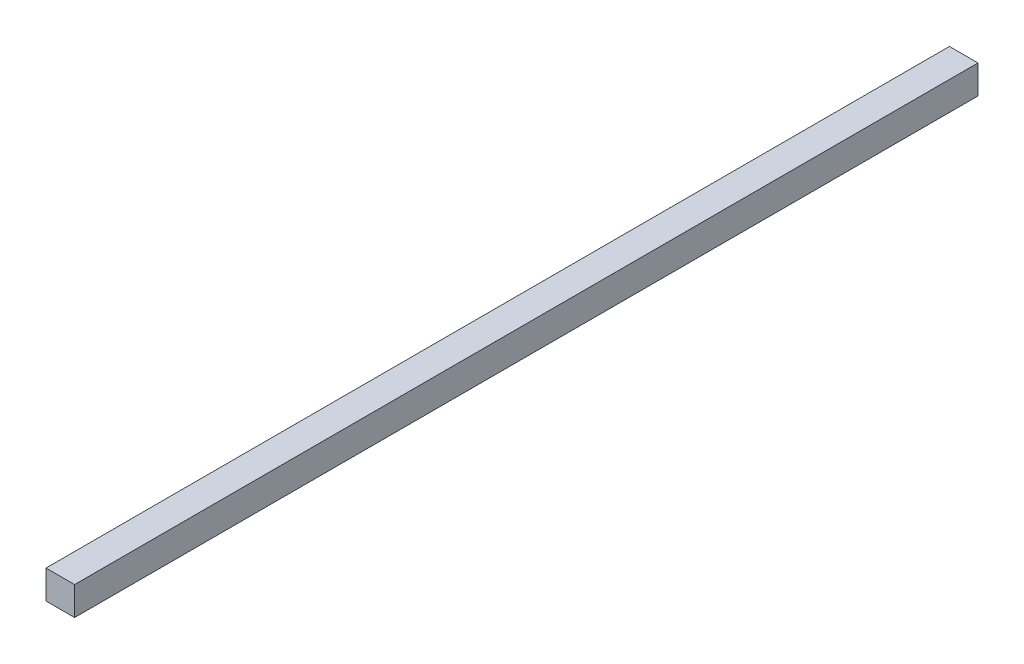
SolidWorks part; units mm, degrees
material "Copper"
ref_plane "Front Plane" through (0, 0, 0) normal (0, 0, 1) x (1, 0, 0)
ref_plane "Top Plane" through (0, 0, 0) normal (0, 1, 0) x (1, 0, 0)
ref_plane "Right Plane" through (0, 0, 0) normal (1, 0, 0) x (0, 0, -1)
sketch "Sketch1" plane through (0, 0, 0) normal (0, 0, 1) x (1, 0, 0)
  line L1 (-1.5875, 1.5875) -> (1.5875, 1.5875)
  line L2 (-1.5875, 1.5875) -> (-1.5875, -1.5875)
  line L3 (-1.5875, -1.5875) -> (1.5875, -1.5875)
  line L4 (1.5875, 1.5875) -> (1.5875, -1.5875)
  line L5 (-1.5875, 1.5875) -> (1.5875, -1.5875) construction
  line L6 (-1.5875, -1.5875) -> (1.5875, 1.5875) construction
  point P0 (0, 0)
  dimension "D1" = 3.175
extrude "Boss-Extrude1" add sketch "Sketch1" along normal blind 100.33
